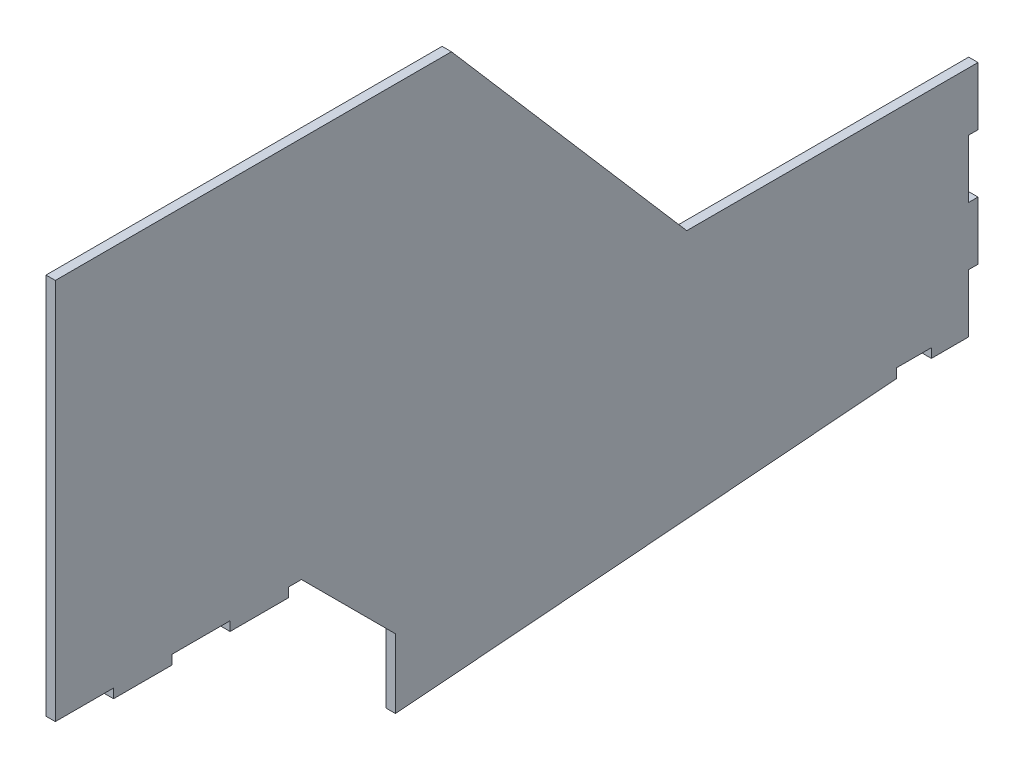
SolidWorks part; units mm, degrees
ref_plane "Alzado" through (0, 0, 0) normal (0, 0, 1) x (1, 0, 0)
ref_plane "Planta" through (0, 0, 0) normal (0, 1, 0) x (1, 0, 0)
ref_plane "Vista lateral" through (0, 0, 0) normal (1, 0, 0) x (0, 0, -1)
sketch "Croquis2" plane through (0, 0, 0) normal (1, 0, 0) x (0, 0, -1)
  line L0 (-196, -75) -> (-90.3534, -75)
  line L1 (-200, 150) -> (200, 150) construction
  line L2 (-200, 150) -> (-200, -150) construction
  line L3 (-200, -150) -> (200, -150) construction
  line L4 (200, 150) -> (200, -150) construction
  line L5 (-200, 150) -> (200, -150) construction
  line L6 (-200, -150) -> (200, 150) construction
  line L11 (-90.3534, -75) -> (-28.5398, -75) construction
  line L17 (-90.3534, -75) -> (-50, -115.3534)
  line L18 (-50, -115.3534) -> (-50, -145)
  line L19 (-50, -145) -> (165, -128)
  line L20 (165, -128) -> (200, -128)
  line L21 (200, -128) -> (200, -28)
  line L22 (200, -28) -> (75, -28)
  line L23 (75, -28) -> (-26, 89)
  line L24 (-26, 89) -> (-196, 89)
  line L25 (-196, 89) -> (-196, -75)
  point P0 (0, 0)
  point P6 (0, 0)
  point P10 (2, 0)
  point P24 (0, 0)
  dimension "D1" = 400
  dimension "D2" = 300
  dimension "D3" = 4
  dimension "D4" = 75
  dimension "D6" = 22
  dimension "D7" = 35
  dimension "D5" = 5
  dimension "D8" = 150
  dimension "D9" = 45
  dimension "D10" = 100
  dimension "D11" = 170
  dimension "D12" = 275
  dimension "D13" = 164
extrude "Saliente-Extruir1" add sketch "Croquis2" along normal blind 4 contours L0 L17 L18 L19 L20 L21 L22 L23 L24 L25 | L0 | L0 region at (0, -32.3047, 18.9642)
sketch "Croquis3" plane through (4, 0, 0) normal (1, 0, 0) x (0, 0, -1)
  line L0 (200, -128) -> (200, -28) construction
  line L1 (200, -53) -> (196, -53)
  line L2 (200, -53) -> (200, -78)
  line L3 (200, -78) -> (196, -78)
  line L4 (196, -53) -> (196, -78)
  line L5 (200, -53) -> (196, -78) construction
  line L6 (200, -78) -> (196, -53) construction
  line L7 (200, -28) -> (200, -53) construction
  line L8 (200, -103) -> (196, -103)
  line L9 (200, -103) -> (200, -128)
  line L10 (200, -128) -> (196, -128)
  line L11 (196, -103) -> (196, -128)
  line L12 (200, -103) -> (196, -128) construction
  line L13 (200, -128) -> (196, -103) construction
  line L14 (200, -78) -> (200, -103) construction
  point P4 (198, -65.5)
  point P11 (198, -115.5)
  dimension "D1" = 25
  dimension "D2" = 4
extrude "Cortar-Extruir1" cut sketch "Croquis3" against normal blind 10
sketch "Croquis4" plane through (4, 0, 0) normal (1, 0, 0) x (0, 0, -1)
  line L0 (-196, -75) -> (-171, -75)
  line L1 (-196, -75) -> (-90.3534, -75) construction
  line L2 (-171, -75) -> (-171, -79)
  line L3 (-171, -79) -> (-146, -79)
  line L4 (-146, -79) -> (-146, -75)
  line L5 (-146, -75) -> (-121, -75)
  line L6 (-121, -75) -> (-121, -79)
  line L7 (-121, -79) -> (-96, -79)
  line L8 (-96, -79) -> (-96, -75)
  line L9 (-96, -75) -> (-71, -75)
  line L10 (-90.3534, -75) -> (-28.5398, -75) construction
  line L11 (-71, -75) -> (-71, -79)
  line L12 (-71, -79) -> (-46, -79)
  line L13 (-46, -79) -> (-46, -75)
  line L14 (-46, -75) -> (-21, -75)
  line L15 (-21, -75) -> (-21, -79)
  line L16 (-21, -79) -> (4, -79)
  line L17 (4, -79) -> (4, -43.9665)
  line L18 (4, -43.9665) -> (4, -42.5047)
  line L19 (4, -42.5047) -> (-196, -42.5047)
  line L20 (-196, 89) -> (-196, -75) construction
  line L21 (-196, -42.5047) -> (-196, -75)
  dimension "D1" = 25
  dimension "D2" = 4
extrude "Saliente-Extruir2" add sketch "Croquis4" against normal blind 4
sketch "Croquis5" plane through (4, 0, 0) normal (1, 0, 0) x (0, 0, -1)
  line L1 (180, -128) -> (165, -128)
  line L2 (180, -128) -> (180, -124)
  line L3 (180, -124) -> (165, -124)
  line L4 (165, -128) -> (165, -124)
  line L5 (180, -128) -> (165, -124) construction
  line L6 (180, -124) -> (165, -128) construction
  point P4 (172.5, -126)
  point P6 (180.8432, -125.1846)
  point P8 (0, 0)
  point P9 (177.5, -126.5656)
  dimension "D2" = 4
  dimension "D1" = 15
  dimension "D3" = 20
extrude "Cortar-Extruir2" cut sketch "Croquis5" against normal blind 10
equation "\"venesta\"= 4'grosor de la venesta"
equation "\"policarbonato\"= 4'grosor del policarbonato"
equation "\"carton_trupan\"= 3'grosor del carton trupan caso laser"
equation "\"ancho_tot\"= 310'ancho tot sin llantas"
equation "\"largo_tot\"= 400'largo tot sin camera"
equation "\"alto_estimado\"= 300'alto estimado sin lidar"
equation "\"D2@Croquis2\"=\"alto_estimado\""
equation "\"D1@Croquis2\"=\"largo_tot\""
equation "\"altoparaqpaselabotella\"= 75'alto estimado para que encaje la botella"
equation "\"alturaruedaloca\"= 22"
equation "\"anchoruedaloca\"= 35"
equation "\"anchopiso1motorybaterias\"= 150"
equation "\"dist-pisorampa\"= 5"
equation "\"D3@Croquis2\"=\"venesta\""
equation "\"D4@Croquis2\"=\"altoparaqpaselabotella\""
equation "\"D6@Croquis2\"=\"alturaruedaloca\""
equation "\"D7@Croquis2\"=\"anchoruedaloca\""
equation "\"D5@Croquis2\"=\"dist-pisorampa\""
equation "\"D8@Croquis2\"=\"anchopiso1motorybaterias\""
equation "\"D10@Croquis2\"= \"paredtrasera\""
equation "\"D11@Croquis2\" = \"anchoultimopiso\""
equation "\"anchoultimopiso\"= 170"
equation "\"paredtrasera\"= 100"
equation "\"agarradorcanasta\"= 275'recolector"
equation "\"D12@Croquis2\"=\"agarradorcanasta\""
equation "\"D13@Croquis2\"= \"alturapiso1y2\" + \"venesta\" + \"alturapiso2y3\""
equation "\"alturapiso1y2\"= 80"
equation "\"alturapiso2y3\"= 80"
equation "\"D1@Saliente-Extruir1\"=\"policarbonato\""
equation "\"D2@Croquis3\"=\"policarbonato\""
equation "\"D2@Croquis4\"=\"venesta\""
equation "\"D1@Saliente-Extruir2\"=\"policarbonato\""
equation "\"D2@Croquis5\"=\"venesta\""
